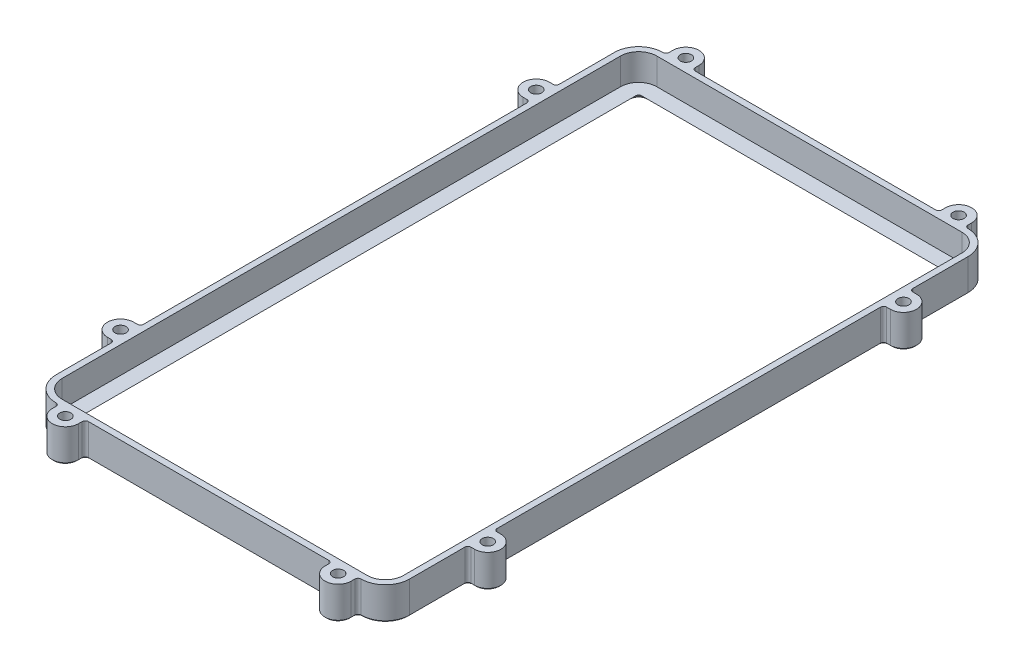
SolidWorks part; units mm, degrees
ref_plane "Front Plane" through (0, 0, 0) normal (0, 0, 1) x (1, 0, 0)
ref_plane "Top Plane" through (0, 0, 0) normal (0, 1, 0) x (1, 0, 0)
ref_plane "Right Plane" through (0, 0, 0) normal (1, 0, 0) x (0, 0, -1)
sketch "Sketch19" plane through (0, 0, 0) normal (0, 1, 0) x (-1, 0, 0)
  line L1 (-6.5603, 44.8694) -> (92.4397, 44.8694)
  line L2 (-14.4403, 36.9894) -> (-14.4403, -144.2106)
  line L3 (-6.5603, -152.0906) -> (92.4397, -152.0906)
  line L4 (100.3197, 36.9894) -> (100.3197, -144.2106)
  arc A0 (-14.4403, -144.2106) -> (-6.5603, -152.0906) centre (-6.5603, -144.2106) ccw
  arc A1 (92.4397, -152.0906) -> (100.3197, -144.2106) centre (92.4397, -144.2106) ccw
  arc A2 (100.3197, 36.9894) -> (92.4397, 44.8694) centre (92.4397, 36.9894) ccw
  arc A3 (-6.5603, 44.8694) -> (-14.4403, 36.9894) centre (-6.5603, 36.9894) ccw
  point P7 (-14.4403, -152.0906)
  point P12 (100.3197, 44.8694)
  point P15 (-14.4403, 44.8694)
  dimension "D5" = 7.88
  dimension "D3" = 114.76
  dimension "D4" = 196.96
extrude "Base" add sketch "Sketch19" along normal blind 10.64
shell "Shell" thickness 2 removed face at (-42.9397, 0, -53.6106) removed face at (-42.9397, 10.64, -53.6106)
sketch "Sketch22" plane through (0, 0, 0) normal (0, -1, 0) x (-1, 0, 0)
  line L0 (-5.5603, 154.2906) -> (-5.5603, 152.0906)
  line L1 (-6.5603, 152.0906) -> (92.4397, 152.0906) construction
  line L2 (-5.5603, 152.0906) -> (2.9397, 152.0906)
  line L3 (2.9397, 152.0906) -> (2.9397, 154.2906)
  line L4 (82.9397, 154.2906) -> (82.9397, 152.0906)
  line L5 (82.9397, 152.0906) -> (91.4397, 152.0906)
  line L6 (91.4397, 152.0906) -> (91.4397, 154.2906)
  line L7 (-5.5603, -47.0694) -> (-5.5603, -44.8694)
  line L8 (92.4397, -44.8694) -> (-6.5603, -44.8694) construction
  line L9 (-5.5603, -44.8694) -> (2.9397, -44.8694)
  line L10 (2.9397, -44.8694) -> (2.9397, -47.0694)
  line L11 (82.9397, -47.0694) -> (82.9397, -44.8694)
  line L12 (82.9397, -44.8694) -> (91.4397, -44.8694)
  line L13 (91.4397, -44.8694) -> (91.4397, -47.0694)
  line L14 (-14.4403, -36.9894) -> (-14.4403, 144.2106) construction
  line L15 (100.3197, 144.2106) -> (100.3197, -36.9894) construction
  line L16 (-14.4403, 53.6106) -> (100.3197, 53.6106) construction
  line L17 (-16.6403, -18.0894) -> (-14.4403, -18.0894)
  line L18 (-14.4403, -18.0894) -> (-14.4403, -9.5894)
  line L19 (-14.4403, -9.5894) -> (-16.6403, -9.5894)
  line L20 (-16.6403, 116.8106) -> (-14.4403, 116.8106)
  line L21 (-14.4403, 116.8106) -> (-14.4403, 125.3106)
  line L22 (-14.4403, 125.3106) -> (-16.6403, 125.3106)
  line L23 (102.5197, 125.3106) -> (100.3197, 125.3106)
  line L24 (100.3197, 125.3106) -> (100.3197, 116.8106)
  line L25 (100.3197, 116.8106) -> (102.5197, 116.8106)
  line L26 (100.3197, -9.5894) -> (102.5197, -9.5894)
  line L27 (100.3197, -9.5894) -> (100.3197, -18.0894)
  line L28 (100.3197, -18.0894) -> (102.5197, -18.0894)
  arc A0 (-5.5603, 154.2906) -> (2.9397, 154.2906) centre (-1.3103, 154.2906) cw
  arc A1 (82.9397, 154.2906) -> (91.4397, 154.2906) centre (87.1897, 154.2906) cw
  arc A2 (-5.5603, -47.0694) -> (2.9397, -47.0694) centre (-1.3103, -47.0694) ccw
  arc A3 (82.9397, -47.0694) -> (91.4397, -47.0694) centre (87.1897, -47.0694) ccw
  arc A4 (-16.6403, 125.3106) -> (-16.6403, 116.8106) centre (-16.6403, 121.0606) ccw
  arc A5 (102.5197, 125.3106) -> (102.5197, 116.8106) centre (102.5197, 121.0606) cw
  arc A6 (102.5197, -9.5894) -> (102.5197, -18.0894) centre (102.5197, -13.8394) cw
  arc A7 (-16.6403, -9.5894) -> (-16.6403, -18.0894) centre (-16.6403, -13.8394) ccw
  dimension "D1" = 8.88
  dimension "D2" = 8.88
  dimension "D3" = 2.2
  dimension "D4" = 8.5
  dimension "D5" = 63.2
  dimension "D6" = 63.2
extrude "Clamps" add sketch "Sketch22" against normal up to surface (10.64 mm away) up to face at (-42.9397, 10.64, -53.6106)
fillet "Clamp Fillets" radius 1 16 edges at (-82.9397, 5.32, 44.8694) (5.5603, 5.32, 44.8694) (-2.9397, 5.32, 44.8694) (-91.4397, 5.32, 44.8694) (-2.9397, 5.32, -152.0906) (-91.4397, 5.32, -152.0906) (-82.9397, 5.32, -152.0906) (5.5603, 5.32, -152.0906) (-100.3197, 5.32, 18.0894) (-100.3197, 5.32, -116.8106) (-100.3197, 5.32, -125.3106) (-100.3197, 5.32, 9.5894) (14.4403, 5.32, -125.3106) (14.4403, 5.32, 9.5894) (14.4403, 5.32, -116.8106) (14.4403, 5.32, 18.0894)
sketch "Sketch25" plane through (0, 0, 0) normal (0, -1, 0) x (1, 0, 0)
  line L24 (14.4403, -144.2106) -> (14.4403, -126.3106)
  line L25 (5.5603, 45.8694) -> (5.5603, 47.0694)
  line L26 (-2.9397, 47.0694) -> (-2.9397, 45.8694)
  line L27 (-3.9397, 44.8694) -> (-81.9397, 44.8694)
  line L28 (-82.9397, 45.8694) -> (-82.9397, 47.0694)
  line L29 (-91.4397, 47.0694) -> (-91.4397, 45.8694)
  line L30 (-100.3197, 36.9894) -> (-100.3197, 19.0894)
  line L31 (-91.4397, -153.0906) -> (-91.4397, -154.2906)
  line L32 (-82.9397, -154.2906) -> (-82.9397, -153.0906)
  line L33 (-81.9397, -152.0906) -> (-3.9397, -152.0906)
  line L34 (-2.9397, -153.0906) -> (-2.9397, -154.2906)
  line L35 (5.5603, -154.2906) -> (5.5603, -153.0906)
  line L36 (14.4403, -144.2106) -> (14.4403, -126.3106)
  line L37 (5.5603, 45.8694) -> (5.5603, 47.0694)
  line L38 (-2.9397, 47.0694) -> (-2.9397, 45.8694)
  line L39 (-3.9397, 44.8694) -> (-81.9397, 44.8694)
  line L40 (-82.9397, 45.8694) -> (-82.9397, 47.0694)
  line L41 (-91.4397, 47.0694) -> (-91.4397, 45.8694)
  line L42 (-100.3197, 36.9894) -> (-100.3197, 19.0894)
  line L43 (-91.4397, -153.0906) -> (-91.4397, -154.2906)
  line L44 (-82.9397, -154.2906) -> (-82.9397, -153.0906)
  line L45 (-81.9397, -152.0906) -> (-3.9397, -152.0906)
  line L46 (-2.9397, -153.0906) -> (-2.9397, -154.2906)
  line L47 (5.5603, -154.2906) -> (5.5603, -153.0906)
  line L48 (6.5603, 37.8694) -> (-92.4397, 37.8694)
  line L49 (-93.3197, 36.9894) -> (-93.3197, -144.2106)
  line L50 (7.4403, -144.2106) -> (7.4403, 36.9894)
  line L51 (-92.4397, -145.0906) -> (6.5603, -145.0906)
  line L52 (6.5603, 37.8694) -> (-92.4397, 37.8694)
  line L53 (-93.3197, 36.9894) -> (-93.3197, -144.2106)
  line L54 (7.4403, -144.2106) -> (7.4403, 36.9894)
  line L55 (-92.4397, -145.0906) -> (6.5603, -145.0906)
  line L60 (15.4403, -125.3106) -> (16.6403, -125.3106)
  line L61 (15.4403, -125.3106) -> (16.6403, -125.3106)
  line L62 (16.6403, -116.8106) -> (15.4403, -116.8106)
  line L63 (16.6403, -116.8106) -> (15.4403, -116.8106)
  line L64 (14.4403, -115.8106) -> (14.4403, 8.5894)
  line L66 (15.4403, 9.5894) -> (16.6403, 9.5894)
  line L67 (15.4403, 9.5894) -> (16.6403, 9.5894)
  line L68 (16.6403, 18.0894) -> (15.4403, 18.0894)
  line L69 (16.6403, 18.0894) -> (15.4403, 18.0894)
  line L70 (14.4403, 19.0894) -> (14.4403, 36.9894)
  line L71 (14.4403, 19.0894) -> (14.4403, 36.9894)
  line L72 (-101.3197, 18.0894) -> (-102.5197, 18.0894)
  line L73 (-101.3197, 18.0894) -> (-102.5197, 18.0894)
  line L74 (-102.5197, 9.5894) -> (-101.3197, 9.5894)
  line L75 (-102.5197, 9.5894) -> (-101.3197, 9.5894)
  line L76 (14.4403, -115.8106) -> (14.4403, 8.5894)
  line L78 (-101.3197, -116.8106) -> (-102.5197, -116.8106)
  line L79 (-101.3197, -116.8106) -> (-102.5197, -116.8106)
  line L80 (-102.5197, -125.3106) -> (-101.3197, -125.3106)
  line L81 (-102.5197, -125.3106) -> (-101.3197, -125.3106)
  line L82 (-100.3197, -126.3106) -> (-100.3197, -144.2106)
  line L83 (-100.3197, -126.3106) -> (-100.3197, -144.2106)
  line L84 (-100.3197, 8.5894) -> (-100.3197, -115.8106)
  line L85 (-100.3197, 8.5894) -> (-100.3197, -115.8106)
  arc A4 (7.4403, 36.9894) -> (6.5603, 37.8694) centre (6.5603, 36.9894) ccw
  arc A5 (7.4403, 36.9894) -> (6.5603, 37.8694) centre (6.5603, 36.9894) ccw
  arc A6 (-92.4397, 37.8694) -> (-93.3197, 36.9894) centre (-92.4397, 36.9894) ccw
  arc A7 (-92.4397, 37.8694) -> (-93.3197, 36.9894) centre (-92.4397, 36.9894) ccw
  arc A8 (6.5603, -145.0906) -> (7.4403, -144.2106) centre (6.5603, -144.2106) ccw
  arc A9 (6.5603, -145.0906) -> (7.4403, -144.2106) centre (6.5603, -144.2106) ccw
  arc A10 (-93.3197, -144.2106) -> (-92.4397, -145.0906) centre (-92.4397, -144.2106) ccw
  arc A11 (-93.3197, -144.2106) -> (-92.4397, -145.0906) centre (-92.4397, -144.2106) ccw
  arc A24 (5.5603, 45.8694) -> (6.5603, 44.8694) centre (6.5603, 45.8694) ccw
  arc A25 (5.5603, 45.8694) -> (6.5603, 44.8694) centre (6.5603, 45.8694) ccw
  arc A26 (-92.4397, 44.8694) -> (-91.4397, 45.8694) centre (-92.4397, 45.8694) ccw
  arc A27 (-92.4397, 44.8694) -> (-91.4397, 45.8694) centre (-92.4397, 45.8694) ccw
  arc A28 (-91.4397, -153.0906) -> (-92.4397, -152.0906) centre (-92.4397, -153.0906) ccw
  arc A29 (-91.4397, -153.0906) -> (-92.4397, -152.0906) centre (-92.4397, -153.0906) ccw
  arc A30 (6.5603, -152.0906) -> (5.5603, -153.0906) centre (6.5603, -153.0906) ccw
  arc A31 (6.5603, -152.0906) -> (5.5603, -153.0906) centre (6.5603, -153.0906) ccw
  arc A32 (6.5603, -152.0906) -> (14.4403, -144.2106) centre (6.5603, -144.2106) ccw
  arc A33 (14.4403, 36.9894) -> (6.5603, 44.8694) centre (6.5603, 36.9894) ccw
  arc A35 (5.5603, 47.0694) -> (-2.9397, 47.0694) centre (1.3103, 47.0694) ccw
  arc A36 (-3.9397, 44.8694) -> (-2.9397, 45.8694) centre (-3.9397, 45.8694) ccw
  arc A37 (-82.9397, 45.8694) -> (-81.9397, 44.8694) centre (-81.9397, 45.8694) ccw
  arc A38 (-82.9397, 47.0694) -> (-91.4397, 47.0694) centre (-87.1897, 47.0694) ccw
  arc A40 (-92.4397, 44.8694) -> (-100.3197, 36.9894) centre (-92.4397, 36.9894) ccw
  arc A41 (-100.3197, -144.2106) -> (-92.4397, -152.0906) centre (-92.4397, -144.2106) ccw
  arc A43 (-91.4397, -154.2906) -> (-82.9397, -154.2906) centre (-87.1897, -154.2906) ccw
  arc A44 (-81.9397, -152.0906) -> (-82.9397, -153.0906) centre (-81.9397, -153.0906) ccw
  arc A45 (-2.9397, -153.0906) -> (-3.9397, -152.0906) centre (-3.9397, -153.0906) ccw
  arc A46 (-2.9397, -154.2906) -> (5.5603, -154.2906) centre (1.3103, -154.2906) ccw
  arc A48 (6.5603, -152.0906) -> (14.4403, -144.2106) centre (6.5603, -144.2106) ccw
  arc A49 (14.4403, 36.9894) -> (6.5603, 44.8694) centre (6.5603, 36.9894) ccw
  arc A51 (5.5603, 47.0694) -> (-2.9397, 47.0694) centre (1.3103, 47.0694) ccw
  arc A52 (-3.9397, 44.8694) -> (-2.9397, 45.8694) centre (-3.9397, 45.8694) ccw
  arc A53 (-82.9397, 45.8694) -> (-81.9397, 44.8694) centre (-81.9397, 45.8694) ccw
  arc A54 (-82.9397, 47.0694) -> (-91.4397, 47.0694) centre (-87.1897, 47.0694) ccw
  arc A56 (-92.4397, 44.8694) -> (-100.3197, 36.9894) centre (-92.4397, 36.9894) ccw
  arc A57 (-100.3197, -144.2106) -> (-92.4397, -152.0906) centre (-92.4397, -144.2106) ccw
  arc A59 (-91.4397, -154.2906) -> (-82.9397, -154.2906) centre (-87.1897, -154.2906) ccw
  arc A60 (-81.9397, -152.0906) -> (-82.9397, -153.0906) centre (-81.9397, -153.0906) ccw
  arc A61 (-2.9397, -153.0906) -> (-3.9397, -152.0906) centre (-3.9397, -153.0906) ccw
  arc A62 (-2.9397, -154.2906) -> (5.5603, -154.2906) centre (1.3103, -154.2906) ccw
  arc A63 (16.6403, -125.3106) -> (16.6403, -116.8106) centre (16.6403, -121.0606) ccw
  arc A64 (16.6403, -125.3106) -> (16.6403, -116.8106) centre (16.6403, -121.0606) ccw
  arc A65 (16.6403, 9.5894) -> (16.6403, 18.0894) centre (16.6403, 13.8394) ccw
  arc A66 (16.6403, 9.5894) -> (16.6403, 18.0894) centre (16.6403, 13.8394) ccw
  arc A67 (-102.5197, 18.0894) -> (-102.5197, 9.5894) centre (-102.5197, 13.8394) ccw
  arc A68 (-102.5197, 18.0894) -> (-102.5197, 9.5894) centre (-102.5197, 13.8394) ccw
  arc A69 (-102.5197, -116.8106) -> (-102.5197, -125.3106) centre (-102.5197, -121.0606) ccw
  arc A70 (-102.5197, -116.8106) -> (-102.5197, -125.3106) centre (-102.5197, -121.0606) ccw
  arc A79 (15.4403, -125.3106) -> (14.4403, -126.3106) centre (15.4403, -126.3106) ccw
  arc A80 (15.4403, -125.3106) -> (14.4403, -126.3106) centre (15.4403, -126.3106) ccw
  arc A81 (14.4403, -115.8106) -> (15.4403, -116.8106) centre (15.4403, -115.8106) ccw
  arc A82 (14.4403, -115.8106) -> (15.4403, -116.8106) centre (15.4403, -115.8106) ccw
  arc A83 (15.4403, 9.5894) -> (14.4403, 8.5894) centre (15.4403, 8.5894) ccw
  arc A84 (15.4403, 9.5894) -> (14.4403, 8.5894) centre (15.4403, 8.5894) ccw
  arc A85 (14.4403, 19.0894) -> (15.4403, 18.0894) centre (15.4403, 19.0894) ccw
  arc A86 (14.4403, 19.0894) -> (15.4403, 18.0894) centre (15.4403, 19.0894) ccw
  arc A87 (-101.3197, 18.0894) -> (-100.3197, 19.0894) centre (-101.3197, 19.0894) ccw
  arc A88 (-101.3197, 18.0894) -> (-100.3197, 19.0894) centre (-101.3197, 19.0894) ccw
  arc A89 (-100.3197, 8.5894) -> (-101.3197, 9.5894) centre (-101.3197, 8.5894) ccw
  arc A90 (-100.3197, 8.5894) -> (-101.3197, 9.5894) centre (-101.3197, 8.5894) ccw
  arc A91 (-101.3197, -116.8106) -> (-100.3197, -115.8106) centre (-101.3197, -115.8106) ccw
  arc A92 (-101.3197, -116.8106) -> (-100.3197, -115.8106) centre (-101.3197, -115.8106) ccw
  arc A93 (-100.3197, -126.3106) -> (-101.3197, -125.3106) centre (-101.3197, -126.3106) ccw
  arc A94 (-100.3197, -126.3106) -> (-101.3197, -125.3106) centre (-101.3197, -126.3106) ccw
  dimension "D1" = 0
  dimension "D2" = 5
extrude "Frame" add sketch "Sketch25" against normal blind 2
chamfer "Frame Chamfer" distance 2 angle 45 8 edges at (-42.9397, 0, 37.8694) (7.4403, 0, -53.6106) (-42.9397, 0, -145.0906) (-93.3197, 0, -53.6106) (7.1825, 0, 37.6116) (7.1825, 0, -144.8329) (-93.062, 0, 37.6116) (-93.062, 0, -144.8329)
sketch "Sketch23" plane through (0, 0, 0) normal (0, -1, 0) x (-1, 0, 0)
  circle A0 centre (-1.3103, 154.2906) radius 1.8
  circle A1 centre (87.1897, 154.2906) radius 1.8
  circle A2 centre (-1.3103, -47.0694) radius 1.8
  circle A3 centre (87.1897, -47.0694) radius 1.8
  arc A4 (2.9397, 154.2906) -> (-5.5603, 154.2906) centre (-1.3103, 154.2906) ccw construction
  arc A5 (91.4397, 154.2906) -> (82.9397, 154.2906) centre (87.1897, 154.2906) ccw construction
  arc A6 (-5.5603, -47.0694) -> (2.9397, -47.0694) centre (-1.3103, -47.0694) ccw construction
  arc A7 (82.9397, -47.0694) -> (91.4397, -47.0694) centre (87.1897, -47.0694) ccw construction
  circle A8 centre (-16.6403, 121.0606) radius 1.8
  circle A9 centre (102.5197, 121.0606) radius 1.8
  circle A10 centre (102.5197, -13.8394) radius 1.8
  circle A11 centre (-16.6403, -13.8394) radius 1.8
  dimension "D1" = 3.6
extrude "Clamp Holes" cut sketch "Sketch23" against normal through all
sketch "Sketch24" plane through (0, 0, 0) normal (0, -1, 0) x (1, 0, 0)
  circle A0 centre (-87.1897, 47.0694) radius 2.9
  circle A1 centre (1.3103, 47.0694) radius 2.9
  circle A2 centre (1.3103, -154.2906) radius 2.9
  circle A3 centre (-87.1897, -154.2906) radius 2.9
  arc A4 (-82.9397, 47.0694) -> (-91.4397, 47.0694) centre (-87.1897, 47.0694) ccw construction
  arc A5 (5.5603, 47.0694) -> (-2.9397, 47.0694) centre (1.3103, 47.0694) ccw construction
  arc A6 (-91.4397, -154.2906) -> (-82.9397, -154.2906) centre (-87.1897, -154.2906) ccw construction
  arc A7 (-2.9397, -154.2906) -> (5.5603, -154.2906) centre (1.3103, -154.2906) ccw construction
  circle A8 centre (16.6403, -121.0606) radius 2.9
  circle A9 centre (-102.5197, -121.0606) radius 2.9
  circle A10 centre (-102.5197, 13.8394) radius 2.9
  circle A11 centre (16.6403, 13.8394) radius 2.9
  dimension "D1" = 5.8
extrude "Clamp Countersinks" cut sketch "Sketch24" against normal blind 3.4
chamfer "Clamp Countersink Chamfers" distance 0.3 angle 45 4 edges at (-87.1897, 0, -157.1906) (1.3103, 0, -157.1906) (1.3103, 0, 44.1694) (-87.1897, 0, 44.1694)
chamfer "Shell Chamfer" distance 0.5 angle 45 52 edges at (-100.3197, 0, 28.0394) (-100.3197, 0, -135.2606) (-98.0117, 0, -149.7826) (-91.7326, 0, -152.3835) (-91.4397, 0, -153.6906) (-87.1897, 0, -158.5406) (-82.9397, 0, -153.6906) (-82.6468, 0, -152.3835) (-42.9397, 0, -152.0906) (-3.2326, 0, -152.3835) (-2.9397, 0, -153.6906) (1.3103, 0, -158.5406) (5.5603, 0, -153.6906) (5.8532, 0, -152.3835) (12.1323, 0, -149.7826) (14.4403, 0, -135.2606) (14.4403, 0, 28.0394) (12.1323, 0, 42.5614) (5.8532, 0, 45.1623) (5.5603, 0, 46.4694) (1.3103, 0, 51.3194) (-2.9397, 0, 46.4694) (-3.2326, 0, 45.1623) (-42.9397, 0, 44.8694) (-82.6468, 0, 45.1623) (-82.9397, 0, 46.4694) (-87.1897, 0, 51.3194) (-91.4397, 0, 46.4694) (-91.7326, 0, 45.1623) (-98.0117, 0, 42.5614) (-100.6126, 0, -125.6035) (14.7332, 0, -125.6035) (-101.9197, 0, -125.3106) (16.0403, 0, -125.3106) (-106.7697, 0, -121.0606) (20.8903, 0, -121.0606) (-101.9197, 0, -116.8106) (16.0403, 0, -116.8106) (-100.6126, 0, -116.5177) (14.7332, 0, -116.5177) (-100.3197, 0, -53.6106) (14.4403, 0, -53.6106) (-100.6126, 0, 9.2965) (14.7332, 0, 9.2965) (-101.9197, 0, 9.5894) (16.0403, 0, 9.5894) (-106.7697, 0, 13.8394) (20.8903, 0, 13.8394) (-101.9197, 0, 18.0894) (16.0403, 0, 18.0894) (-100.6126, 0, 18.3823) (14.7332, 0, 18.3823)
